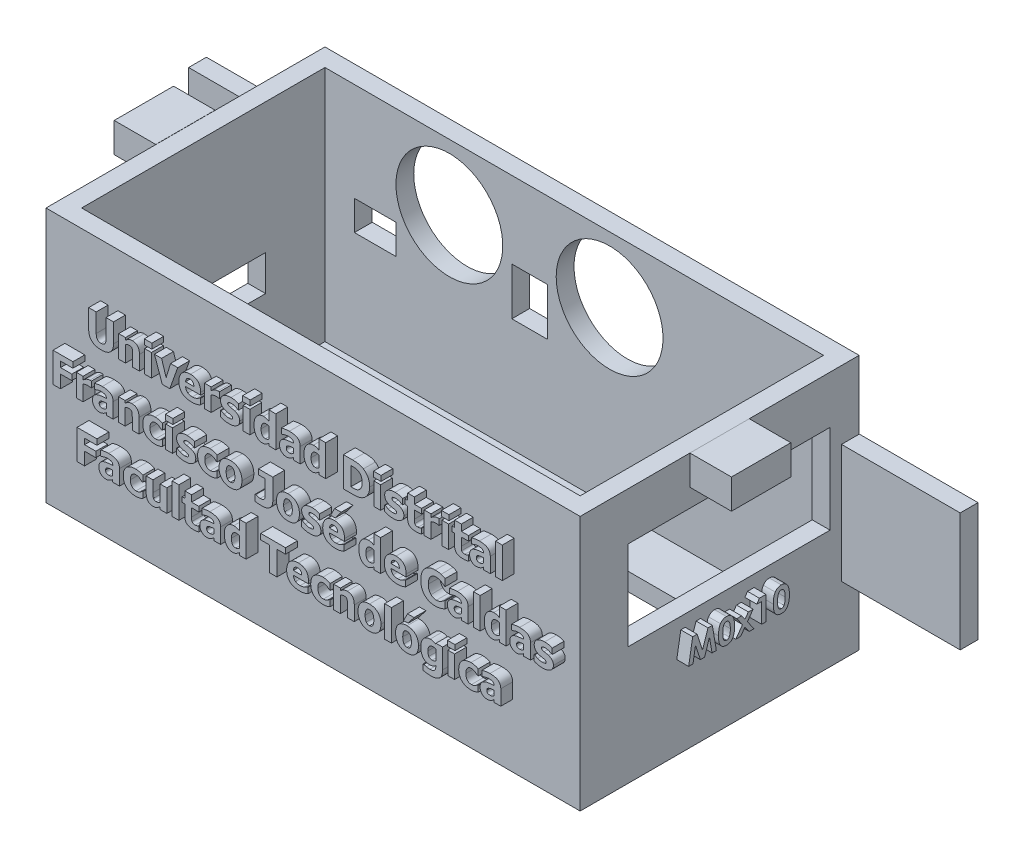
SolidWorks part; units mm, degrees
ref_plane "Alzado" through (0, 0, 0) normal (0, 0, 1) x (1, 0, 0)
ref_plane "Planta" through (0, 0, 0) normal (0, 1, 0) x (1, 0, 0)
ref_plane "Vista lateral" through (0, 0, 0) normal (1, 0, 0) x (0, 0, -1)
sketch "Croquis1" plane through (0, 0, 0) normal (0, 1, 0) x (1, 0, 0)
  line L1 (-45, 23.5) -> (45, 23.5)
  line L2 (-45, 23.5) -> (-45, -23.5)
  line L3 (-45, -23.5) -> (45, -23.5)
  line L4 (45, 23.5) -> (45, -23.5)
  line L5 (-45, 23.5) -> (45, -23.5) construction
  line L6 (-45, -23.5) -> (45, 23.5) construction
  point P0 (0, 0)
extrude "Saliente-Extruir1" add sketch "Croquis1" along normal blind 3
sketch "Croquis2" plane through (0, 3, 0) normal (0, 1, 0) x (1, 0, 0)
  line L1 (-42, 20.5) -> (42, 20.5)
  line L2 (-42, 20.5) -> (-42, -20.5)
  line L3 (-42, -20.5) -> (42, -20.5)
  line L4 (42, 20.5) -> (42, -20.5)
  line L5 (-42, 20.5) -> (42, -20.5) construction
  line L6 (-42, -20.5) -> (42, 20.5) construction
  line L9 (45, 23.5) -> (-45, 23.5) construction
  line L10 (-45, 23.5) -> (-45, -23.5) construction
  line L11 (45, -23.5) -> (45, 23.5) construction
  line L12 (-45, -23.5) -> (45, -23.5) construction
  line L13 (45, 23.5) -> (-45, 23.5)
  line L14 (-45, 23.5) -> (-45, -23.5)
  line L15 (45, -23.5) -> (45, 23.5)
  line L16 (-45, -23.5) -> (45, -23.5)
  point P0 (0, 0)
extrude "Saliente-Extruir2" add sketch "Croquis2" along normal blind 40
sketch "Croquis6" plane through (0, 0, 0) normal (0, -1, 0) x (-1, 0, 0)
  line L1 (36.0091, -12.4705) -> (-35.9909, -12.4705)
  line L2 (36.0091, -12.4705) -> (36.0091, 12.5295)
  line L3 (36.0091, 12.5295) -> (-35.9909, 12.5295)
  line L4 (-35.9909, -12.4705) -> (-35.9909, 12.5295)
extrude "Cortar-Extruir5" cut sketch "Croquis6" against normal blind 3
sketch "Croquis8" plane through (45, 0, 0) normal (1, 0, 0) x (0, 0, -1)
  line L5 (-15.4013, 34.9423) -> (18.5987, 34.9423)
  line L6 (-15.4013, 34.9423) -> (-15.4013, 19.9423)
  line L7 (-15.4013, 19.9423) -> (18.5987, 19.9423)
  line L8 (18.5987, 34.9423) -> (18.5987, 19.9423)
extrude "Cortar-Extruir6" cut sketch "Croquis8" against normal blind 3
sketch "Croquis9" plane through (45, 0, 0) normal (1, 0, 0) x (0, 0, -1)
  line L2 (-5.0086, 43.0022) -> (4.9914, 43.0022)
  line L3 (-5.0086, 43.0022) -> (-5.0086, 38.0022)
  line L4 (-5.0086, 38.0022) -> (4.9914, 38.0022)
  line L5 (4.9914, 43.0022) -> (4.9914, 38.0022)
extrude "Saliente-Extruir3" add sketch "Croquis9" along normal blind 7
sketch "Croquis10" plane through (45, 0, 0) normal (1, 0, 0) x (0, 0, -1)
  line L2 (20.5283, 31.4936) -> (23.5283, 31.4936)
  line L3 (20.5283, 31.4936) -> (20.5283, 11.4936)
  line L4 (20.5283, 11.4936) -> (23.5283, 11.4936)
  line L5 (23.5283, 31.4936) -> (23.5283, 11.4936)
extrude "Saliente-Extruir4" add sketch "Croquis10" along normal blind 20
sketch "Croquis12" plane through (-45, 0, 0) normal (-1, 0, 0) x (0, 0, 1)
  line L1 (-23.5294, 31.4856) -> (-20.5294, 31.4856)
  line L2 (-23.5294, 31.4856) -> (-23.5294, 11.4856)
  line L3 (-23.5294, 11.4856) -> (-20.5294, 11.4856)
  line L4 (-20.5294, 31.4856) -> (-20.5294, 11.4856)
extrude "Saliente-Extruir5" add sketch "Croquis12" along normal blind 20
sketch "Croquis13" plane through (-45, 0, 0) normal (-1, 0, 0) x (0, 0, 1)
  line L2 (-4.9927, 43.0287) -> (5.0073, 43.0287)
  line L3 (-4.9927, 43.0287) -> (-4.9927, 38.0287)
  line L4 (-4.9927, 38.0287) -> (5.0073, 38.0287)
  line L5 (5.0073, 43.0287) -> (5.0073, 38.0287)
extrude "Saliente-Extruir6" add sketch "Croquis13" along normal blind 7
sketch "Croquis14" plane through (-45, 0, 0) normal (-1, 0, 0) x (0, 0, 1)
  line L1 (-10.5011, 21.0075) -> (0.4989, 21.0075)
  line L2 (-10.5011, 21.0075) -> (-10.5011, 15.0075)
  line L3 (-10.5011, 15.0075) -> (0.4989, 15.0075)
  line L4 (0.4989, 21.0075) -> (0.4989, 15.0075)
  line L5 (-23.5, 43) -> (-23.5, 31.4856) construction
extrude "Cortar-Extruir8" cut sketch "Croquis14" against normal blind 3
sketch "Croquis15" plane through (0, 0, -23.5) normal (0, 0, -1) x (-1, 0, 0)
  line L14 (30.0381, 26.3981) -> (37.0381, 26.3981)
  line L15 (30.0381, 26.3981) -> (30.0381, 21.3981)
  line L16 (30.0381, 21.3981) -> (37.0381, 21.3981)
  line L17 (37.0381, 26.3981) -> (37.0381, 21.3981)
  line L20 (4.5108, 30.0753) -> (10.5108, 30.0753)
  line L21 (4.5108, 30.0753) -> (4.5108, 22.0753)
  line L22 (4.5108, 22.0753) -> (10.5108, 22.0753)
  line L23 (10.5108, 30.0753) -> (10.5108, 22.0753)
  circle A0 centre (-5.9583, 31.9461) radius 9
  circle A1 centre (21.0417, 31.9461) radius 9
  dimension "D1" = 5
extrude "Cortar-Extruir9" cut sketch "Croquis15" against normal blind 3
sketch "Croquis16" plane through (0, 0, 23.5) normal (0, 0, 1) x (1, 0, 0)
  text T0 "   Universidad Distrital\r\nFrancisco José de Caldas\r\n  Facultad Tecnológica" font "Tahoma" height 5
extrude "Saliente-Extruir7" add sketch "Croquis16" along normal blind 2
sketch "Croquis18" plane through (45, 0, 0) normal (1, 0, 0) x (0, 0, -1)
  text T0 "M0x10" font "Century Gothic" height 4
extrude "Saliente-Extruir9" add sketch "Croquis18" along normal blind 2
